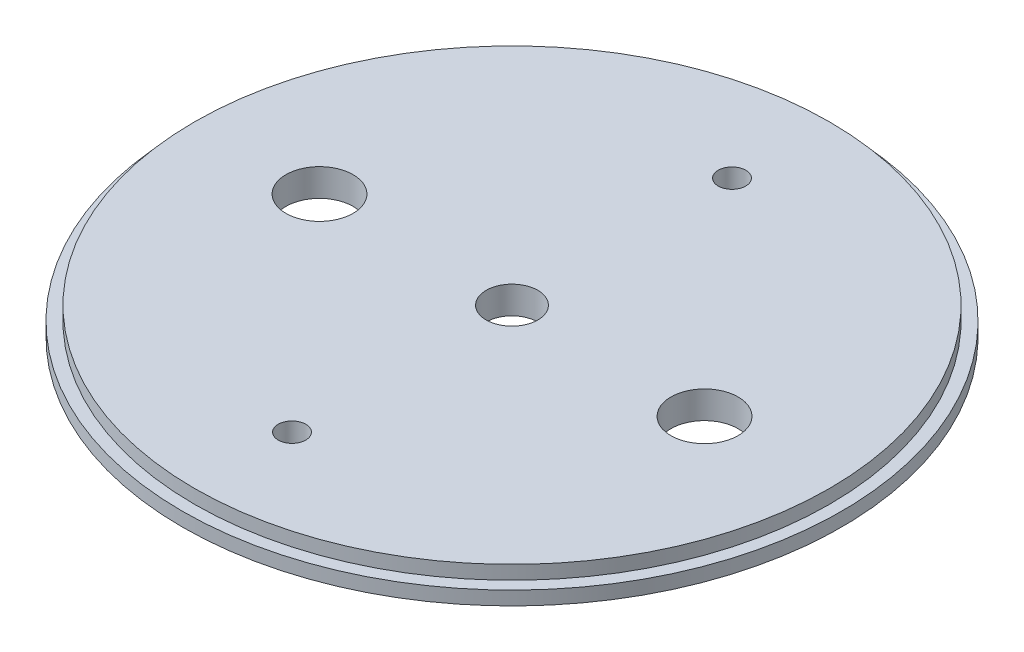
SolidWorks part; units mm, degrees
material "6061-T6 (SS)"
ref_plane "Front Plane" through (0, 0, 0) normal (0, 0, 1) x (1, 0, 0)
ref_plane "Top Plane" through (0, 0, 0) normal (0, 1, 0) x (1, 0, 0)
ref_plane "Right Plane" through (0, 0, 0) normal (1, 0, 0) x (0, 0, -1)
sketch "Sketch1" plane through (0, 0, 0) normal (0, 1, 0) x (1, 0, 0)
  circle A0 centre (0, 0) radius 73.3171
  circle A1 centre (0, 0) radius 76.0984
  dimension "D1" = 146.6342
  dimension "D2" = 152.1968
extrude "Boss-Extrude1" add sketch "Sketch1" along normal blind 3.175 contours A0 | A1 A0 region at (0, 0, 0) region at (-73.946, 0, 0)
extrude "Boss-Extrude2" add sketch "Sketch1<3>" along normal blind 6.35 contours A0 region at (0, 0, 0)
sketch "Sketch1<3>" plane through (0, 0, 0) normal (0, 1, 0) x (1, 0, 0) same geometry as "Sketch1"
sketch "Sketch3" plane through (0, 0, 0) normal (0, -1, 0) x (1, 0, 0)
  line L0 (44.45, 0) -> (-44.45, 0) construction
  line L1 (0, -50.8) -> (0, 50.8) construction
  circle A0 centre (0, 0) radius 5.9531
  circle A1 centre (-44.45, 0) radius 8.25
  circle A2 centre (44.45, 0) radius 8.25
  circle A3 centre (0, 50.8) radius 4.9609
  circle A4 centre (0, -50.8) radius 4.9609
  point P6 (0, 0)
  point P14 (0, 0)
  dimension "D1" = 11.9062
  dimension "D2" = 16.5001
  dimension "D3" = 9.9219
  dimension "D4" = 101.6
  dimension "D5" = 88.9
hole_wizard "1/4 (0.25) Diameter Hole1" positions "Sketch4" profile "Sketch5" hole size "1/4" standard "ANSI Inch" end condition through all
sketch "Sketch4" plane through (0, 0, 0) normal (0, -1, 0) x (-1, 0, 0)
  point P0 (0, 50.8)
  point P3 (0, -50.8)
sketch "Sketch5" plane through (0, 0, -50.8) normal (1, 0, 0) x (0, 0, -1)
  line L0 (0, 0) -> (0, 6.35)
  line L1 (0, 6.35) -> (3.175, 6.35)
  line L2 (3.175, 6.35) -> (3.175, 0)
  line L5 (3.175, 0) -> (0, 0)
  line L11 (0, -6.35) -> (0, 107.95) construction
  dimension "Thru Hole Dia." = 6.35
  dimension "Thru Hole Depth" = 6.35
extrude "Cut-Extrude1" [suppressed] cut sketch "Sketch3" against normal through all
hole_wizard "M18x2.5 Tapped Hole1" positions "Sketch6" profile "Sketch7" tap size "M18x2.5" standard "ANSI Metric" end condition through all
sketch "Sketch6" plane through (0, 0, 0) normal (0, -1, 0) x (-1, 0, 0)
  point P0 (44.45, 0)
  point P3 (-44.45, 0)
sketch "Sketch7" plane through (-44.45, 0, 0) normal (1, 0, 0) x (0, 0, -1)
  line L0 (0, 0) -> (0, 6.35)
  line L1 (0, 6.35) -> (7.75, 6.35)
  line L2 (7.75, 6.35) -> (7.75, 0)
  line L5 (7.75, 0) -> (0, 0)
  line L11 (0, -6.35) -> (0, 107.95) construction
  dimension "Thru Tap Drill Dia." = 15.5
  dimension "Thru Tap Drill Depth" = 6.35
cosmetic thread "Hole Thread1" parameters "D2"=18
cosmetic thread "Hole Thread2" parameters "D2"=18
extrude "Cut-Extrude2" cut sketch "Sketch3<3>" against normal through all contours A0
sketch "Sketch3<3>" plane through (0, 0, 0) normal (0, -1, 0) x (1, 0, 0) same geometry as "Sketch3"
